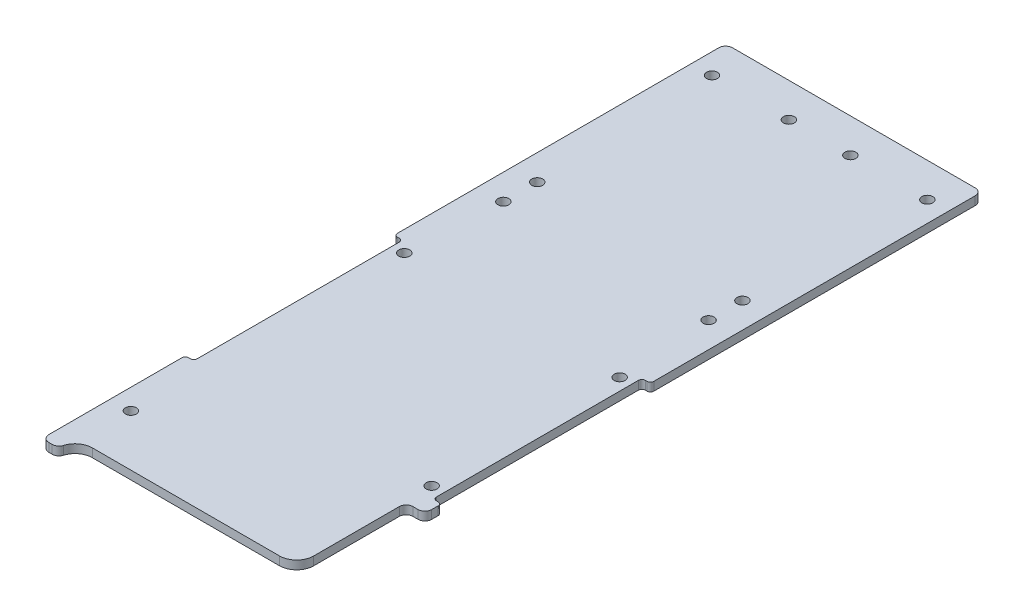
SolidWorks part; units mm, degrees
ref_plane "Front Plane" through (0, 0, 0) normal (0, 0, 1) x (1, 0, 0)
ref_plane "Top Plane" through (0, 0, 0) normal (0, 1, 0) x (1, 0, 0)
ref_plane "Right Plane" through (0, 0, 0) normal (1, 0, 0) x (0, 0, -1)
sketch "Sketch1" plane through (0, 0, 0) normal (0, 1, 0) x (1, 0, 0)
  line L0 (-39.9997, 0) -> (-39.9997, 114.3) construction
  line L1 (-47.625, 127) -> (47.625, 127)
  line L2 (-47.625, 127) -> (-47.625, -127)
  line L3 (-47.625, -127) -> (47.625, -127)
  line L4 (47.625, 127) -> (47.625, -127)
  line L5 (-47.625, 127) -> (47.625, -127) construction
  line L6 (-47.625, -127) -> (47.625, 127) construction
  line L7 (0, 0) -> (0, 127) construction
  line L8 (-39.9997, 0) -> (-39.9997, -101.6) construction
  line L9 (-39.9997, 0) -> (0, 0) construction
  line L10 (-41.275, -127) -> (-41.275, -120.65)
  line L11 (-41.275, -120.65) -> (41.275, -120.65)
  line L12 (41.275, -120.65) -> (41.275, -127)
  line L13 (-39.9997, 114.3) -> (-11.4247, 114.3) construction
  line L14 (39.9997, 114.3) -> (11.4247, 114.3) construction
  circle A0 centre (-39.9997, 114.3) radius 2.032
  circle A1 centre (-39.9997, 0) radius 2.032
  circle A2 centre (-39.9997, -101.6) radius 2.032
  circle A3 centre (39.9997, -101.6) radius 2.032
  circle A4 centre (39.9997, 0) radius 2.032
  circle A5 centre (39.9997, 114.3) radius 2.032
  circle A6 centre (-11.4247, 114.3) radius 2.032
  circle A7 centre (11.4247, 114.3) radius 2.032
  circle A8 centre (-39.9997, -69.85) radius 2.032
  circle A9 centre (39.9997, -69.85) radius 2.032
  point P0 (0, 0)
  dimension "D4" = 4.064
  dimension "D10" = 28.575
  dimension "D1" = 95.25
  dimension "D2" = 254
  dimension "D3" = 7.6253
  dimension "D5" = 12.7
  dimension "D6" = 25.4
  dimension "D7" = 6.35
  dimension "D8" = 6.35
  dimension "D9" = 6.35
  dimension "D11" = 69.85
extrude "Boss-Extrude1" add sketch "Sketch1" along normal blind 3.175 contours L4 L1 L2 L3 A4 A0 A1 A2 A3 A5 | A8 | A3 region at (0, 0, -2.6944) region at (39.9997, 0, 101.6) region at (-39.9997, 0, 69.85)
fillet "Fillet1" radius 2.54 4 edges at (-47.625, 1.5875, -127) (47.625, 1.5875, -127) (47.625, 1.5875, 127) (-47.625, 1.5875, 127)
fillet "Fillet2" radius 2.54 2 edges at (41.275, 1.5875, 127) (-41.275, 1.5875, 127)
fillet "Fillet3" radius 6.35 2 edges at (41.275, 1.5875, 120.65) (-41.275, 1.5875, 120.65)
sketch "Sketch2" plane through (0, 0, 0) normal (0, -1, 0) x (1, 0, 0)
  line L0 (41.9112, 131.8831) -> (41.9112, 109.8659) construction
  line L1 (41.9112, 109.8659) -> (41.9112, 106.3879) construction
  line L2 (41.9112, 83.271) -> (41.9112, 82.5325) construction
  line L3 (41.9112, 82.5325) -> (41.9112, 81.2514) construction
  line L4 (41.9112, 83.271) -> (41.9112, 106.3879) construction
  line L5 (41.9112, 131.8831) -> (41.9112, 109.8659)
  line L6 (41.9112, 109.8659) -> (41.9112, 106.3879)
  line L7 (41.9112, 83.271) -> (41.9112, 82.5325)
  line L8 (41.9112, 82.5325) -> (41.9112, 81.2514)
  line L9 (41.9112, 83.271) -> (41.9112, 106.3879)
  line L10 (41.9112, 81.2514) -> (47.625, 81.2514)
  line L11 (47.625, -124.46) -> (47.625, 124.46) construction
  line L12 (41.9112, 131.8831) -> (47.625, 131.8831)
  line L13 (47.625, 131.8831) -> (47.625, 81.2514)
  line L14 (40.6412, 79.9814) -> (48.895, 79.9814)
  line L15 (48.895, 133.1531) -> (48.895, 79.9814)
  line L16 (40.6412, 133.1531) -> (48.895, 133.1531)
  line L17 (40.6412, 133.1531) -> (40.6412, 109.8659)
  line L18 (40.6412, 109.8659) -> (40.6412, 106.3879)
  line L19 (40.6412, 83.271) -> (40.6412, 106.3879)
  line L20 (40.6412, 83.271) -> (40.6412, 82.5325)
  line L21 (40.6412, 82.5325) -> (40.6412, 79.9814)
  arc M7 (43.815, 127) -> (41.3809, 125.1857) centre (43.815, 124.46) ccw
  arc M8 (41.3809, 125.1857) -> (35.2956, 120.65) centre (35.2956, 127) cw
  line M18 (47.625, -124.46) -> (47.625, 124.46)
  dimension "D1" = 1.27
extrude "Cut-Extrude1" cut sketch "Sketch2" against normal through all contours L20 L21 L14 L10 L8 L7 L9 L19 M18 | L19 L9 L6 L5 L17 L18 M7 M8 | L13 L10 L8 L7 L9 L6 L5 L12 region at (41.6763, 0, 99.9804)
fillet "Fillet4" radius 6.35 1 edges at (40.6412, 1.5875, 123.5727)
fillet "Fillet5" radius 2.54 2 edges at (47.625, 1.5875, 79.9814) (40.6412, 1.5875, 79.9814)
sketch "Sketch3" plane through (0, 0, 0) normal (0, -1, 0) x (1, 0, 0)
  line L0 (-36.3093, -49.7791) -> (-39.9161, -49.7791) construction
  line L1 (-40.4241, -49.276) -> (-40.4241, -45.7043) construction
  line L2 (-35.8013, -45.7043) -> (-35.8013, -49.276) construction
  line L3 (-39.9161, -45.2013) -> (-36.3093, -45.2013) construction
  line L4 (-36.3093, -37.2027) -> (-39.9161, -37.2027) construction
  line L5 (-35.8013, -33.1279) -> (-35.8013, -36.6996) construction
  line L6 (-40.4241, -36.6996) -> (-40.4241, -33.1279) construction
  line L7 (-39.9161, -32.6249) -> (-36.3093, -32.6249) construction
  line L8 (36.2839, -32.6249) -> (39.8907, -32.6249) construction
  line L9 (40.3987, -33.1279) -> (40.3987, -36.6996) construction
  line L10 (39.8907, -37.2027) -> (36.2839, -37.2027) construction
  line L11 (35.7759, -36.6996) -> (35.7759, -33.1279) construction
  line L12 (36.2839, -45.2013) -> (39.8907, -45.2013) construction
  line L13 (35.7759, -49.276) -> (35.7759, -45.7043) construction
  line L14 (40.3987, -45.7043) -> (40.3987, -49.276) construction
  line L15 (39.8907, -49.7791) -> (36.2839, -49.7791) construction
  line L16 (-36.3093, -49.7791) -> (-39.9161, -49.7791)
  line L17 (-40.4241, -49.276) -> (-40.4241, -45.7043)
  line L18 (-35.8013, -45.7043) -> (-35.8013, -49.276)
  line L19 (-39.9161, -45.2013) -> (-36.3093, -45.2013)
  line L20 (-36.3093, -37.2027) -> (-39.9161, -37.2027)
  line L21 (-35.8013, -33.1279) -> (-35.8013, -36.6996)
  line L22 (-40.4241, -36.6996) -> (-40.4241, -33.1279)
  line L23 (-39.9161, -32.6249) -> (-36.3093, -32.6249)
  line L24 (36.2839, -32.6249) -> (39.8907, -32.6249)
  line L25 (40.3987, -33.1279) -> (40.3987, -36.6996)
  line L26 (39.8907, -37.2027) -> (36.2839, -37.2027)
  line L27 (35.7759, -36.6996) -> (35.7759, -33.1279)
  line L28 (36.2839, -45.2013) -> (39.8907, -45.2013)
  line L29 (35.7759, -49.276) -> (35.7759, -45.7043)
  line L30 (40.3987, -45.7043) -> (40.3987, -49.276)
  line L31 (39.8907, -49.7791) -> (36.2839, -49.7791)
  line L32 (-47.625, -25.836) -> (47.625, -25.836)
  line L33 (-47.625, -124.46) -> (-47.625, 124.46) construction
  line L34 (47.625, -124.46) -> (47.625, 77.4414) construction
  line L35 (0, -25.836) -> (0, -56.0686) construction
  line L38 (134.3615, -51.414) -> (184.1373, -51.414)
  line L39 (184.1373, -51.414) -> (184.1373, -43.4909)
  line L40 (184.1373, -43.4909) -> (182.3339, -43.4909)
  line L41 (181.8259, -42.9878) -> (181.8259, -39.4161)
  line L42 (182.3339, -38.9131) -> (184.1373, -38.9131)
  line L43 (184.1373, -38.9131) -> (184.1373, -30.9899)
  line L44 (184.1373, -30.9899) -> (134.3615, -30.9899)
  line L45 (134.3615, -30.9899) -> (133.3373, -32.0042)
  line L46 (133.3373, -32.0042) -> (132.3131, -30.9899)
  line L47 (132.3131, -30.9899) -> (70.8615, -30.9899)
  line L48 (70.8615, -30.9899) -> (69.8373, -32.0042)
  line L49 (69.8373, -32.0042) -> (68.8131, -30.9899)
  line L50 (68.8131, -30.9899) -> (7.3615, -30.9899)
  line L51 (7.3615, -30.9899) -> (6.3373, -32.0042)
  line L52 (6.3373, -32.0042) -> (5.3131, -30.9899)
  line L53 (5.3131, -30.9899) -> (-56.1385, -30.9899)
  line L54 (-56.1385, -30.9899) -> (-57.1627, -32.0042)
  line L55 (-57.1627, -32.0042) -> (-58.1869, -30.9899)
  line L56 (-58.1869, -30.9899) -> (-119.6385, -30.9899)
  line L57 (-119.6385, -30.9899) -> (-120.6627, -32.0042)
  line L58 (-120.6627, -32.0042) -> (-121.6869, -30.9899)
  line L59 (-121.6869, -30.9899) -> (-184.1627, -30.9899)
  line L60 (-184.1627, -30.9899) -> (-184.1627, -51.414)
  line L61 (-184.1627, -51.414) -> (-121.6869, -51.414)
  line L62 (-121.6869, -51.414) -> (-120.6627, -50.3998)
  line L63 (-120.6627, -50.3998) -> (-119.6385, -51.414)
  line L64 (-119.6385, -51.414) -> (-58.1869, -51.414)
  line L65 (-58.1869, -51.414) -> (-57.1627, -50.3998)
  line L66 (-57.1627, -50.3998) -> (-56.1385, -51.414)
  line L67 (-56.1385, -51.414) -> (5.3131, -51.414)
  line L68 (5.3131, -51.414) -> (6.3373, -50.3998)
  line L69 (6.3373, -50.3998) -> (7.3615, -51.414)
  line L70 (7.3615, -51.414) -> (68.8131, -51.414)
  line L71 (68.8131, -51.414) -> (69.8373, -50.3998)
  line L72 (69.8373, -50.3998) -> (70.8615, -51.414)
  line L73 (70.8615, -51.414) -> (132.3131, -51.414)
  line L74 (132.3131, -51.414) -> (133.3373, -50.3998)
  line L75 (133.3373, -50.3998) -> (134.3615, -51.414)
  line L76 (134.3615, -51.414) -> (184.1373, -51.414)
  line L77 (184.1373, -51.414) -> (184.1373, -43.4909)
  line L78 (184.1373, -43.4909) -> (182.3339, -43.4909)
  line L79 (181.8259, -42.9878) -> (181.8259, -39.4161)
  line L80 (182.3339, -38.9131) -> (184.1373, -38.9131)
  line L81 (184.1373, -38.9131) -> (184.1373, -30.9899)
  line L82 (184.1373, -30.9899) -> (134.3615, -30.9899)
  line L83 (134.3615, -30.9899) -> (133.3373, -32.0042)
  line L84 (133.3373, -32.0042) -> (132.3131, -30.9899)
  line L85 (132.3131, -30.9899) -> (70.8615, -30.9899)
  line L86 (70.8615, -30.9899) -> (69.8373, -32.0042)
  line L87 (69.8373, -32.0042) -> (68.8131, -30.9899)
  line L88 (68.8131, -30.9899) -> (7.3615, -30.9899)
  line L89 (7.3615, -30.9899) -> (6.3373, -32.0042)
  line L90 (6.3373, -32.0042) -> (5.3131, -30.9899)
  line L91 (5.3131, -30.9899) -> (-56.1385, -30.9899)
  line L92 (-56.1385, -30.9899) -> (-57.1627, -32.0042)
  line L93 (-57.1627, -32.0042) -> (-58.1869, -30.9899)
  line L94 (-58.1869, -30.9899) -> (-119.6385, -30.9899)
  line L95 (-119.6385, -30.9899) -> (-120.6627, -32.0042)
  line L96 (-120.6627, -32.0042) -> (-121.6869, -30.9899)
  line L97 (-121.6869, -30.9899) -> (-184.1627, -30.9899)
  line L98 (-184.1627, -30.9899) -> (-184.1627, -51.414)
  line L99 (-184.1627, -51.414) -> (-121.6869, -51.414)
  line L100 (-121.6869, -51.414) -> (-120.6627, -50.3998)
  line L101 (-120.6627, -50.3998) -> (-119.6385, -51.414)
  line L102 (-119.6385, -51.414) -> (-58.1869, -51.414)
  line L103 (-58.1869, -51.414) -> (-57.1627, -50.3998)
  line L104 (-57.1627, -50.3998) -> (-56.1385, -51.414)
  line L105 (-56.1385, -51.414) -> (5.3131, -51.414)
  line L106 (5.3131, -51.414) -> (6.3373, -50.3998)
  line L107 (6.3373, -50.3998) -> (7.3615, -51.414)
  line L108 (7.3615, -51.414) -> (68.8131, -51.414)
  line L109 (68.8131, -51.414) -> (69.8373, -50.3998)
  line L110 (69.8373, -50.3998) -> (70.8615, -51.414)
  line L111 (70.8615, -51.414) -> (132.3131, -51.414)
  line L112 (132.3131, -51.414) -> (133.3373, -50.3998)
  line L113 (133.3373, -50.3998) -> (134.3615, -51.414)
  line L1362 (-40.4241, -34.9138) -> (-35.8013, -34.9138)
  line L1857 (-38.1127, -32.6249) -> (-38.1127, -37.2027)
  line L1858 (-38.1127, -45.2013) -> (-38.1127, -49.7791)
  line L1859 (-40.4241, -47.4902) -> (-35.8013, -47.4902)
  circle A0 centre (-38.1127, -34.9138) radius 2.032
  circle A1 centre (-38.1127, -47.4902) radius 2.032
  circle A2 centre (38.1127, -47.4902) radius 2.032
  circle A3 centre (38.1127, -34.9138) radius 2.032
  ellipse E0 centre (-39.9161, -45.7043) end of major axis (-39.4081, -45.7043) minor radius 0.5031 (-39.9161, -45.2013) -> (-40.4241, -45.7043) ccw construction
  ellipse E1 centre (-39.9161, -49.276) end of major axis (-39.4081, -49.276) minor radius 0.5031 (-40.4241, -49.276) -> (-39.9161, -49.7791) ccw construction
  ellipse E2 centre (182.3339, -42.9878) end of major axis (182.8419, -42.9878) minor radius 0.5031 (181.8259, -42.9878) -> (182.3339, -43.4909) ccw
  ellipse E3 centre (182.3339, -39.4161) end of major axis (182.8419, -39.4161) minor radius 0.5031 (182.3339, -38.9131) -> (181.8259, -39.4161) ccw
  ellipse E4 centre (182.3339, -42.9878) end of major axis (182.8419, -42.9878) minor radius 0.5031 (181.8259, -42.9878) -> (182.3339, -43.4909) ccw
  ellipse E5 centre (182.3339, -39.4161) end of major axis (182.8419, -39.4161) minor radius 0.5031 (182.3339, -38.9131) -> (181.8259, -39.4161) ccw
  ellipse E6 centre (-36.3093, -49.276) end of major axis (-35.8013, -49.276) minor radius 0.5031 (-36.3093, -49.7791) -> (-35.8013, -49.276) ccw construction
  ellipse E7 centre (-36.3093, -45.7043) end of major axis (-35.8013, -45.7043) minor radius 0.5031 (-35.8013, -45.7043) -> (-36.3093, -45.2013) ccw construction
  ellipse E8 centre (-39.9161, -36.6996) end of major axis (-39.4081, -36.6996) minor radius 0.5031 (-40.4241, -36.6996) -> (-39.9161, -37.2027) ccw construction
  ellipse E9 centre (-36.3093, -36.6996) end of major axis (-35.8013, -36.6996) minor radius 0.5031 (-36.3093, -37.2027) -> (-35.8013, -36.6996) ccw construction
  ellipse E10 centre (-36.3093, -33.1279) end of major axis (-35.8013, -33.1279) minor radius 0.5031 (-35.8013, -33.1279) -> (-36.3093, -32.6249) ccw construction
  ellipse E11 centre (-39.9161, -33.1279) end of major axis (-39.4081, -33.1279) minor radius 0.5031 (-39.9161, -32.6249) -> (-40.4241, -33.1279) ccw construction
  ellipse E12 centre (39.8907, -33.1279) end of major axis (40.3987, -33.1279) minor radius 0.5031 (40.3987, -33.1279) -> (39.8907, -32.6249) ccw construction
  ellipse E13 centre (36.2839, -33.1279) end of major axis (36.7919, -33.1279) minor radius 0.5031 (36.2839, -32.6249) -> (35.7759, -33.1279) ccw construction
  ellipse E14 centre (39.8907, -36.6996) end of major axis (40.3987, -36.6996) minor radius 0.5031 (39.8907, -37.2027) -> (40.3987, -36.6996) ccw construction
  ellipse E15 centre (36.2839, -36.6996) end of major axis (36.7919, -36.6996) minor radius 0.5031 (35.7759, -36.6996) -> (36.2839, -37.2027) ccw construction
  ellipse E16 centre (36.2839, -45.7043) end of major axis (36.7919, -45.7043) minor radius 0.5031 (36.2839, -45.2013) -> (35.7759, -45.7043) ccw construction
  ellipse E17 centre (36.2839, -49.276) end of major axis (36.7919, -49.276) minor radius 0.5031 (35.7759, -49.276) -> (36.2839, -49.7791) ccw construction
  ellipse E18 centre (39.8907, -45.7043) end of major axis (40.3987, -45.7043) minor radius 0.5031 (40.3987, -45.7043) -> (39.8907, -45.2013) ccw construction
  ellipse E19 centre (39.8907, -49.276) end of major axis (40.3987, -49.276) minor radius 0.5031 (39.8907, -49.7791) -> (40.3987, -49.276) ccw construction
  ellipse E20 centre (-39.9161, -45.7043) end of major axis (-39.4081, -45.7043) minor radius 0.5031 (-39.9161, -45.2013) -> (-40.4241, -45.7043) ccw
  ellipse E21 centre (-39.9161, -49.276) end of major axis (-39.4081, -49.276) minor radius 0.5031 (-40.4241, -49.276) -> (-39.9161, -49.7791) ccw
  ellipse E22 centre (-36.3093, -49.276) end of major axis (-35.8013, -49.276) minor radius 0.5031 (-36.3093, -49.7791) -> (-35.8013, -49.276) ccw
  ellipse E23 centre (-36.3093, -45.7043) end of major axis (-35.8013, -45.7043) minor radius 0.5031 (-35.8013, -45.7043) -> (-36.3093, -45.2013) ccw
  ellipse E24 centre (-39.9161, -36.6996) end of major axis (-39.4081, -36.6996) minor radius 0.5031 (-40.4241, -36.6996) -> (-39.9161, -37.2027) ccw
  ellipse E25 centre (-36.3093, -36.6996) end of major axis (-35.8013, -36.6996) minor radius 0.5031 (-36.3093, -37.2027) -> (-35.8013, -36.6996) ccw
  ellipse E26 centre (-36.3093, -33.1279) end of major axis (-35.8013, -33.1279) minor radius 0.5031 (-35.8013, -33.1279) -> (-36.3093, -32.6249) ccw
  ellipse E27 centre (-39.9161, -33.1279) end of major axis (-39.4081, -33.1279) minor radius 0.5031 (-39.9161, -32.6249) -> (-40.4241, -33.1279) ccw
  ellipse E28 centre (39.8907, -33.1279) end of major axis (40.3987, -33.1279) minor radius 0.5031 (40.3987, -33.1279) -> (39.8907, -32.6249) ccw
  ellipse E29 centre (36.2839, -33.1279) end of major axis (36.7919, -33.1279) minor radius 0.5031 (36.2839, -32.6249) -> (35.7759, -33.1279) ccw
  ellipse E30 centre (39.8907, -36.6996) end of major axis (40.3987, -36.6996) minor radius 0.5031 (39.8907, -37.2027) -> (40.3987, -36.6996) ccw
  ellipse E31 centre (36.2839, -36.6996) end of major axis (36.7919, -36.6996) minor radius 0.5031 (35.7759, -36.6996) -> (36.2839, -37.2027) ccw
  ellipse E32 centre (36.2839, -45.7043) end of major axis (36.7919, -45.7043) minor radius 0.5031 (36.2839, -45.2013) -> (35.7759, -45.7043) ccw
  ellipse E33 centre (36.2839, -49.276) end of major axis (36.7919, -49.276) minor radius 0.5031 (35.7759, -49.276) -> (36.2839, -49.7791) ccw
  ellipse E34 centre (39.8907, -45.7043) end of major axis (40.3987, -45.7043) minor radius 0.5031 (40.3987, -45.7043) -> (39.8907, -45.2013) ccw
  ellipse E35 centre (39.8907, -49.276) end of major axis (40.3987, -49.276) minor radius 0.5031 (39.8907, -49.7791) -> (40.3987, -49.276) ccw
  dimension "D2" = 4.064
  dimension "D1" = 0
extrude "Cut-Extrude2" cut sketch "Sketch3" against normal through all contours A0 | A1 | A2 | A3
sketch "Sketch4" plane through (0, 3.175, 0) normal (0, 1, 0) x (1, 0, 0)
  line L0 (-44.45, 3.81) -> (-46.99, 3.81) construction
  line L1 (-46.99, 3.81) -> (-46.99, 121.92) construction
  line L2 (-42.545, 126.365) -> (-0.635, 126.365) construction
  line L3 (-0.635, 126.365) -> (-0.635, 107.95) construction
  line L4 (-6.35, 102.235) -> (-15.875, 102.235) construction
  line L5 (-22.86, 95.25) -> (-22.86, -115.57) construction
  line L6 (-27.305, -120.015) -> (-35.4551, -120.015) construction
  line L7 (-43.815, -126.365) -> (-45.085, -126.365) construction
  line L8 (-46.99, -124.46) -> (-46.99, -73.7819) construction
  line L9 (-46.99, -73.7819) -> (-44.45, -73.7819) construction
  line L10 (-44.45, -73.7819) -> (-44.45, 3.81) construction
  line L11 (-46.99, 3.81) -> (-44.45, 3.81)
  line L12 (-46.99, 121.92) -> (-46.99, 3.81)
  line L13 (-0.635, 126.365) -> (-42.545, 126.365)
  line L14 (-0.635, 107.95) -> (-0.635, 126.365)
  line L15 (-15.875, 102.235) -> (-6.35, 102.235)
  line L16 (-22.86, -115.57) -> (-22.86, 95.25)
  line L17 (-35.4551, -120.015) -> (-27.305, -120.015)
  line L18 (-45.085, -126.365) -> (-43.815, -126.365)
  line L19 (-46.99, -73.7819) -> (-46.99, -124.46)
  line L20 (-44.45, -73.7819) -> (-46.99, -73.7819)
  line L21 (-44.45, 3.81) -> (-44.45, -73.7819)
  line L22 (-46.99, 3.81) -> (-44.45, 3.81)
  line L23 (-46.99, 121.92) -> (-46.99, 3.81)
  line L24 (-0.635, 126.365) -> (-42.545, 126.365)
  line L25 (-0.635, 107.95) -> (-0.635, 126.365)
  line L26 (-15.875, 102.235) -> (-6.35, 102.235)
  line L27 (-22.86, -115.57) -> (-22.86, 95.25)
  line L28 (-35.4551, -120.015) -> (-27.305, -120.015)
  line L29 (-45.085, -126.365) -> (-43.815, -126.365)
  line L30 (-46.99, -73.7819) -> (-46.99, -124.46)
  line L31 (-44.45, -73.7819) -> (-46.99, -73.7819)
  line L32 (-44.45, 3.81) -> (-44.45, -73.7819)
  line L33 (40.64, -77.5286) -> (40.64, -117.0408) construction
  line L34 (35.4551, -120.015) -> (27.305, -120.015) construction
  line L35 (22.86, -115.57) -> (22.86, 95.25) construction
  line L36 (15.875, 102.235) -> (6.35, 102.235) construction
  line L37 (0.635, 107.95) -> (0.635, 126.365) construction
  line L38 (0.635, 126.365) -> (42.545, 126.365) construction
  line L39 (46.99, 121.92) -> (46.99, 3.81) construction
  line L40 (46.99, 3.81) -> (44.45, 3.81) construction
  line L41 (44.45, 3.81) -> (44.45, -73.7819) construction
  line L42 (44.45, -73.7819) -> (46.99, -73.7819) construction
  line L43 (46.99, -73.7819) -> (46.99, -77.5286) construction
  line L44 (46.99, -77.5286) -> (40.64, -77.5286) construction
  line L45 (-44.45, 3.81) -> (-46.99, 3.81)
  line L46 (-46.99, 3.81) -> (-46.99, 121.92)
  line L47 (-42.545, 126.365) -> (-0.635, 126.365)
  line L48 (-0.635, 126.365) -> (-0.635, 107.95)
  line L49 (-6.35, 102.235) -> (-15.875, 102.235)
  line L50 (-22.86, 95.25) -> (-22.86, -115.57)
  line L51 (-27.305, -120.015) -> (-35.4551, -120.015)
  line L52 (-43.815, -126.365) -> (-45.085, -126.365)
  line L53 (-46.99, -124.46) -> (-46.99, -73.7819)
  line L54 (-46.99, -73.7819) -> (-44.45, -73.7819)
  line L55 (-44.45, -73.7819) -> (-44.45, 3.81)
  line L56 (40.64, -77.5286) -> (40.64, -117.0408)
  line L57 (35.4551, -120.015) -> (27.305, -120.015)
  line L58 (22.86, -115.57) -> (22.86, 95.25)
  line L59 (15.875, 102.235) -> (6.35, 102.235)
  line L60 (0.635, 107.95) -> (0.635, 126.365)
  line L61 (0.635, 126.365) -> (42.545, 126.365)
  line L62 (46.99, 121.92) -> (46.99, 3.81)
  line L63 (46.99, 3.81) -> (44.45, 3.81)
  line L64 (44.45, 3.81) -> (44.45, -73.7819)
  line L65 (44.45, -73.7819) -> (46.99, -73.7819)
  line L66 (46.99, -73.7819) -> (46.99, -77.5286)
  line L67 (46.99, -77.5286) -> (40.64, -77.5286)
  line L178 (-46.99, 3.81) -> (-47.625, 3.81)
  line L179 (-47.625, 124.46) -> (-47.625, -124.46) construction
  line L180 (-46.99, -73.7819) -> (-47.625, -73.7819)
  line L181 (46.99, -73.7819) -> (47.625, -73.7819)
  line L182 (47.625, 124.46) -> (47.625, -77.4414) construction
  line L183 (46.99, 3.81) -> (47.625, 3.81)
  arc A0 (-42.545, 126.365) -> (-46.99, 121.92) centre (-42.545, 121.92) ccw construction
  arc A1 (-6.35, 102.235) -> (-0.635, 107.95) centre (-6.35, 107.95) ccw construction
  arc A2 (-15.875, 102.235) -> (-22.86, 95.25) centre (-15.875, 95.25) ccw construction
  arc A3 (-27.305, -120.015) -> (-22.86, -115.57) centre (-27.305, -115.57) ccw construction
  arc A4 (-35.4551, -120.015) -> (-41.9138, -124.3399) centre (-35.4551, -127) ccw construction
  arc A5 (-43.815, -126.365) -> (-41.9138, -124.3399) centre (-43.815, -124.46) ccw construction
  arc A6 (-46.99, -124.46) -> (-45.085, -126.365) centre (-45.085, -124.46) ccw construction
  arc A7 (-42.545, 126.365) -> (-46.99, 121.92) centre (-42.545, 121.92) ccw
  arc A8 (-6.35, 102.235) -> (-0.635, 107.95) centre (-6.35, 107.95) ccw
  arc A9 (-15.875, 102.235) -> (-22.86, 95.25) centre (-15.875, 95.25) ccw
  arc A10 (-27.305, -120.015) -> (-22.86, -115.57) centre (-27.305, -115.57) ccw
  arc A11 (-35.4551, -120.015) -> (-41.9138, -124.3399) centre (-35.4551, -127) ccw
  arc A12 (-43.815, -126.365) -> (-41.9138, -124.3399) centre (-43.815, -124.46) ccw
  arc A13 (-46.99, -124.46) -> (-45.085, -126.365) centre (-45.085, -124.46) ccw
  arc A14 (-42.545, 126.365) -> (-46.99, 121.92) centre (-42.545, 121.92) ccw
  arc A15 (-6.35, 102.235) -> (-0.635, 107.95) centre (-6.35, 107.95) ccw
  arc A16 (-15.875, 102.235) -> (-22.86, 95.25) centre (-15.875, 95.25) ccw
  arc A17 (-27.305, -120.015) -> (-22.86, -115.57) centre (-27.305, -115.57) ccw
  arc A18 (-35.4551, -120.015) -> (-41.9138, -124.3399) centre (-35.4551, -127) ccw
  arc A19 (-43.815, -126.365) -> (-41.9138, -124.3399) centre (-43.815, -124.46) ccw
  arc A20 (-46.99, -124.46) -> (-45.085, -126.365) centre (-45.085, -124.46) ccw
  arc A21 (36.8369, -120.153) -> (40.64, -117.0408) centre (37.465, -117.0408) ccw construction
  arc A22 (36.8369, -120.153) -> (35.4551, -120.015) centre (35.4551, -127) ccw construction
  arc A23 (22.86, -115.57) -> (27.305, -120.015) centre (27.305, -115.57) ccw construction
  arc A24 (22.86, 95.25) -> (15.875, 102.235) centre (15.875, 95.25) ccw construction
  arc A25 (0.635, 107.95) -> (6.35, 102.235) centre (6.35, 107.95) ccw construction
  arc A26 (46.99, 121.92) -> (42.545, 126.365) centre (42.545, 121.92) ccw construction
  arc A27 (-42.545, 126.365) -> (-46.99, 121.92) centre (-42.545, 121.92) ccw
  arc A28 (-6.35, 102.235) -> (-0.635, 107.95) centre (-6.35, 107.95) ccw
  arc A29 (-15.875, 102.235) -> (-22.86, 95.25) centre (-15.875, 95.25) ccw
  arc A30 (-27.305, -120.015) -> (-22.86, -115.57) centre (-27.305, -115.57) ccw
  arc A31 (-35.4551, -120.015) -> (-41.9138, -124.3399) centre (-35.4551, -127) ccw
  arc A32 (-43.815, -126.365) -> (-41.9138, -124.3399) centre (-43.815, -124.46) ccw
  arc A33 (-46.99, -124.46) -> (-45.085, -126.365) centre (-45.085, -124.46) ccw
  arc A34 (36.8369, -120.153) -> (40.64, -117.0408) centre (37.465, -117.0408) ccw
  arc A35 (36.8369, -120.153) -> (35.4551, -120.015) centre (35.4551, -127) ccw
  arc A36 (22.86, -115.57) -> (27.305, -120.015) centre (27.305, -115.57) ccw
  arc A37 (22.86, 95.25) -> (15.875, 102.235) centre (15.875, 95.25) ccw
  arc A38 (0.635, 107.95) -> (6.35, 102.235) centre (6.35, 107.95) ccw
  arc A39 (46.99, 121.92) -> (42.545, 126.365) centre (42.545, 121.92) ccw
  line M32 (47.625, -77.4414) -> (47.625, 124.46)
  line M36 (-47.625, 124.46) -> (-47.625, -124.46)
  dimension "D1" = 0
extrude "Cut-Extrude3" cut sketch "Sketch4" against normal through all and the other way through all contours L180 L31 L32 L22 L178 M36 | L183 L63 L64 L65 L181 M32 region at (-46.0375, 3.175, 34.9859) region at (46.0375, 3.175, 34.9859)
fillet "Fillet6" radius 1.27 8 edges at (-44.45, 1.5875, -3.81) (-44.45, 1.5875, 73.7819) (44.45, 1.5875, -3.81) (44.45, 1.5875, 73.7819) (47.625, 1.5875, 73.7819) (47.625, 1.5875, -3.81) (-47.625, 1.5875, 73.7819) (-47.625, 1.5875, -3.81)
